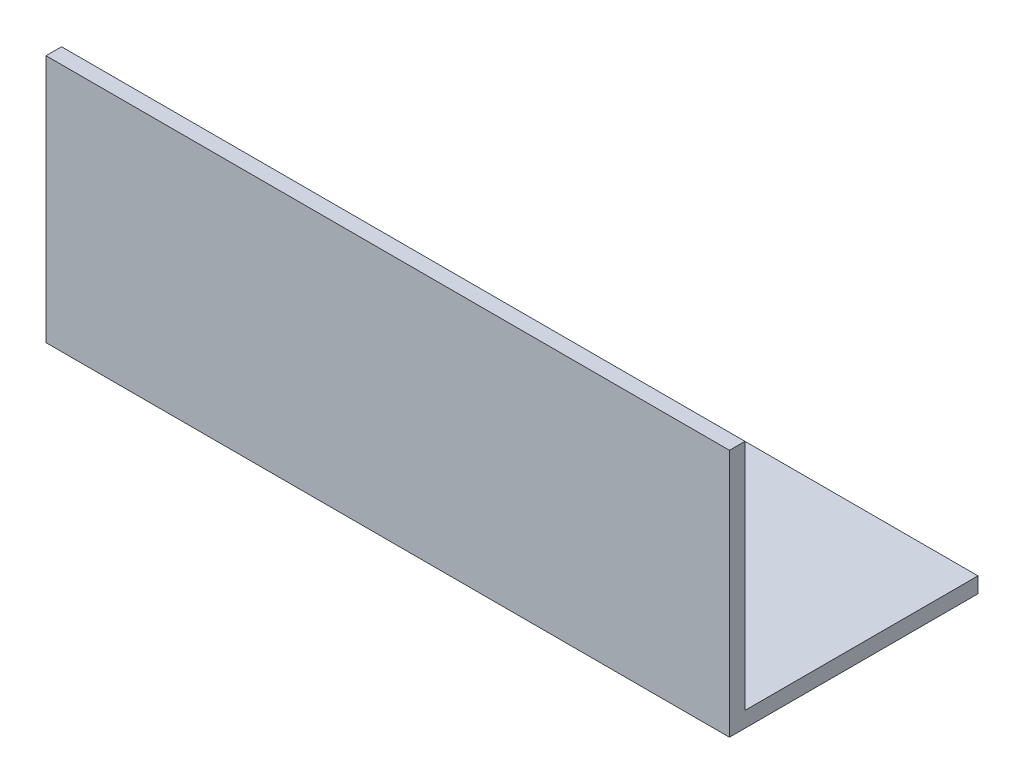
SolidWorks part; units mm, degrees
ref_plane "Спереди" through (0, 0, 0) normal (0, 0, 1) x (1, 0, 0)
ref_plane "Сверху" through (0, 0, 0) normal (0, 1, 0) x (1, 0, 0)
ref_plane "Справа" through (0, 0, 0) normal (1, 0, 0) x (0, 0, -1)
sketch "Эскиз1" plane through (0, 0, 0) normal (1, 0, 0) x (0, 0, -1)
  line L0 (0, 0) -> (0, 75)
  line L1 (0, 0) -> (75, 0)
extrude "Вытянуть-Тонкостенный1" add sketch "Эскиз1" along normal blind 220 thin thin type one direction wall 5
